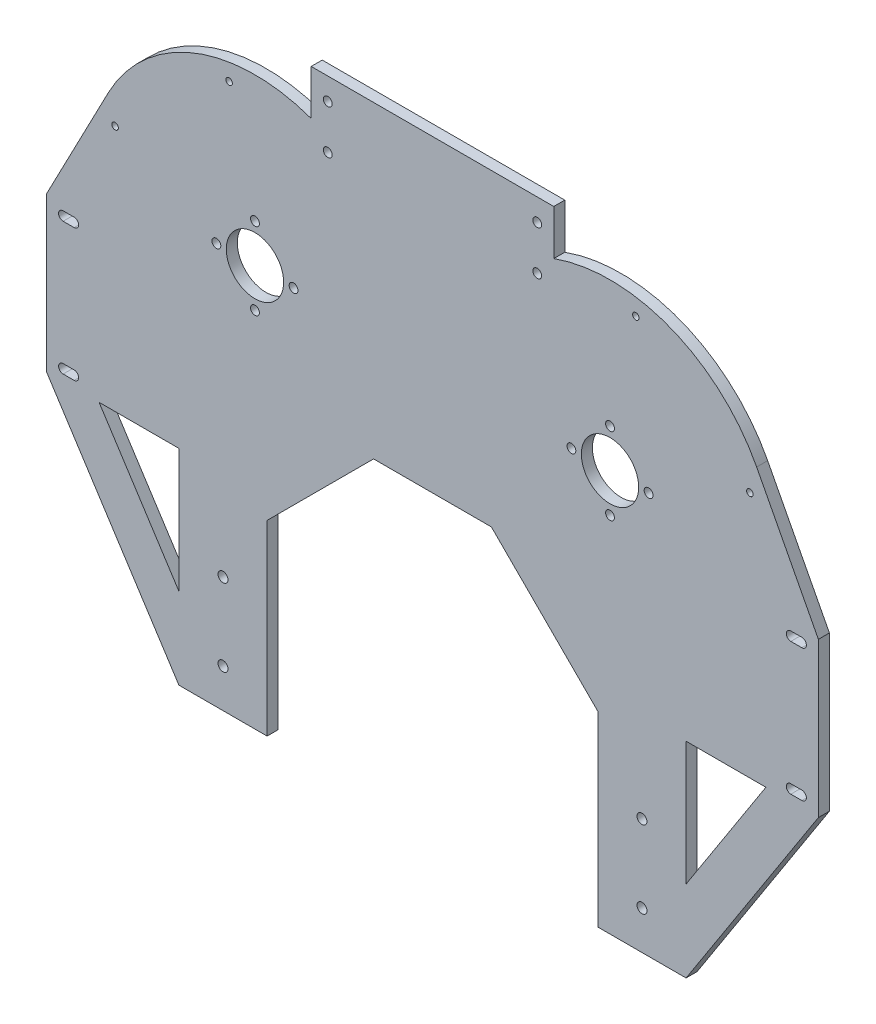
SolidWorks part; units mm, degrees
ref_plane "Front Plane" through (0, 0, 0) normal (0, 0, 1) x (1, 0, 0)
ref_plane "Top Plane" through (0, 0, 0) normal (0, 1, 0) x (1, 0, 0)
ref_plane "Right Plane" through (0, 0, 0) normal (1, 0, 0) x (0, 0, -1)
sketch "Sketch1" plane through (0, 0, 0) normal (0, 0, 1) x (1, 0, 0)
  line L1 (-100, -75) -> (100, -75)
  line L2 (-100, -75) -> (-100, 75)
  line L3 (-100, 75) -> (100, 75)
  line L4 (100, -75) -> (100, 75)
  line L5 (-100, -75) -> (100, 75) construction
  line L6 (-100, 75) -> (100, -75) construction
  line L8 (-47.5, 40) -> (47.5, 40) construction
  line L9 (0, 75) -> (0, -75) construction
  line L10 (-27, -44) -> (27, -44) construction
  line L11 (-27, -44) -> (-27, 28) construction
  line L12 (-27, 28) -> (27, 28) construction
  line L13 (27, -44) -> (27, 28) construction
  line L14 (-27, -44) -> (27, 28) construction
  line L15 (-27, 28) -> (27, -44) construction
  line L23 (-55, 70) -> (55, 70)
  line L24 (-55, 70) -> (-55, -70)
  line L25 (-55, -70) -> (55, -70)
  line L26 (55, 70) -> (55, -70)
  line L27 (-55, 70) -> (55, -70) construction
  line L28 (-55, -70) -> (55, 70) construction
  line L29 (-32.5, 70) -> (32.5, 70) construction
  line L30 (-32.5, 70) -> (-32.5, 55) construction
  line L31 (-32.5, 55) -> (32.5, 55) construction
  line L32 (32.5, 70) -> (32.5, 55) construction
  line L33 (-32.5, 70) -> (32.5, 55) construction
  line L34 (-32.5, 55) -> (32.5, 70) construction
  circle A2 centre (-47.5, 40) radius 2
  circle A3 centre (47.5, 40) radius 2
  circle A4 centre (-27, 28) radius 2 construction
  circle A5 centre (27, 28) radius 2 construction
  circle A6 centre (27, -44) radius 2 construction
  circle A7 centre (-27, -44) radius 2 construction
  circle A8 centre (-47.5, 60) radius 2
  circle A10 centre (47.5, 60) radius 2
  point P0 (0, 0)
  point P15 (0, 40)
  point P18 (0, -8)
  point P56 (0, 0)
  point P63 (0, 62.5)
  dimension "D3" = 4
  dimension "D4" = 20
  dimension "D5" = 4
  dimension "D8" = 4
  dimension "D1" = 150
  dimension "D2" = 200
  dimension "D6" = 72
  dimension "D7" = 54
  dimension "D14" = 30
  dimension "D15" = 140
  dimension "D16" = 110
  dimension "D17" = 95
  dimension "D18" = 12
  dimension "D19" = 15
  dimension "D20" = 65
extrude "Boss-Extrude1" add sketch "Sketch1" along normal blind 5 contours L23 L32 L31 L30 L24 L25 L26 A7 A6 A5 A4 A3 A2 region at (0, -0.1637, 0)
sketch "Sketch2" plane through (0, 0, 0) normal (0, 0, 1) x (1, 0, 0)
  line L0 (-55, -70) -> (-100.8579, -115.8579) construction
  line L1 (-55, 70) -> (-55, -70) construction
  line L2 (-55, -41.7157) -> (-115, -101.7157)
  line L3 (-26.7157, -70) -> (-86.7157, -130)
  line L4 (-55, -70) -> (55, -70) construction
  line L5 (-115, -101.7157) -> (-86.7157, -130)
  line L6 (-115, -101.7157) -> (-115, -203)
  line L7 (-75, -118.2843) -> (-75, -203)
  line L8 (-75, -203) -> (-115, -203)
  line L9 (0, 75) -> (0, -75) construction
  line L10 (-55, -41.7157) -> (-26.7157, -70)
  line L11 (-55, 70) -> (-55, -70) construction
  line L12 (-115, -203) -> (-75, -203) construction
  circle A0 centre (-95, -150.5) radius 2.25
  circle A1 centre (-95, -185.5) radius 2.25
  circle A2 centre (-95, -150.5) radius 2.25 construction
  circle A4 centre (-95, -185.5) radius 2.25 construction
  dimension "D1" = 135
  dimension "D2" = 40
  dimension "D3" = 40
  dimension "D4" = 75
  dimension "D5" = 0
extrude "Boss-Extrude2" add sketch "Sketch2" along normal blind 5 contours L8 L7 L3 L5 L6 | L10 L2 L5 L3 region at (-70.8579, -85.8579, 0) region at (-95.9307, -160.1869, 0)
mirror "Mirror1" about plane through (0, 0, 0) normal (1, 0, 0) of "Boss-Extrude2"
sketch "Sketch3" plane through (0, 0, 5) normal (0, 0, 1) x (1, 0, 0)
  line L0 (0, 31.3301) -> (0, 52.1198) construction
  line L1 (-80.5, -21) -> (-92.2213, 45.4745) construction
  line L2 (-80.5, -21) -> (80.5, -21) construction
  line L3 (-80.5, -21) -> (-148, -21) construction
  line L4 (-80.5, -21) -> (-143.9293, 2.0864) construction
  circle A0 centre (-80.5, -21) radius 75
  circle A1 centre (-80.5, -3.5) radius 2
  circle A2 centre (80.5, -21) radius 75
  circle A3 centre (-80.5, -21) radius 60
  circle A4 centre (80.5, -21) radius 60
  circle A5 centre (-47.5, 40) radius 2 construction
  circle A6 centre (-47.5, 40) radius 2
  circle A7 centre (47.5, 40) radius 2
  circle A8 centre (-63, -21) radius 2
  circle A9 centre (-80.5, -38.5) radius 2
  circle A10 centre (-98, -21) radius 2
  circle A11 centre (98, -21) radius 2
  circle A12 centre (80.5, -38.5) radius 2
  circle A13 centre (63, -21) radius 2
  circle A14 centre (80.5, -3.5) radius 2
  circle A15 centre (-80.5, -21) radius 13
  circle A16 centre (80.5, -21) radius 13
  circle A17 centre (-92.2213, 45.4745) radius 1.4732
  circle A18 centre (-143.9293, 2.0864) radius 1.4732
  circle A19 centre (-80.5, -21) radius 67.5 construction
  circle A20 centre (92.2213, 45.4745) radius 1.4732
  circle A21 centre (143.9293, 2.0864) radius 1.4732
  point P28 (-80.5, -21)
  line M3 (115, -101.7157) -> (55, -41.7157)
  line M4 (55, -41.7157) -> (55, 70)
  line M6 (-55, 70) -> (-55, -41.7157)
  line M7 (-55, -41.7157) -> (-115, -101.7157)
  line M11 (-75, -118.2843) -> (-26.7157, -70)
  line M12 (-26.7157, -70) -> (26.7157, -70)
  line M13 (26.7157, -70) -> (75, -118.2843)
  circle M17 centre (-47.5, 40) radius 2
  circle M18 centre (47.5, 40) radius 2
  dimension "D1" = 161
  dimension "D2" = 150
  dimension "D3" = 61
  dimension "D4" = 120
  dimension "D5" = 4
  dimension "D7" = 35
  dimension "D8" = 26
  dimension "D9" = 7.5
  dimension "D10" = 2.9464
  dimension "D6" = 4
  dimension "D11" = 80
  dimension "D12" = 20
extrude "Boss-Extrude3" add sketch "Sketch3" against normal up to surface (5 mm away) contours A3 M6 M7 | A3 A0 M6 M7 | A3 A0 M7 M11 M12 M6 M17 | A3 M7 M6 | A4 M3 M4 | A4 M4 M3 | A4 A2 M4 M3 | A4 A2 M3 M4 M12 M13 M18 region at (-11.8554, -46.5242, 5) region at (9.6495, -2.4591, 5) region at (-56.7712, 41.4218, 5) region at (-96.2806, -16.4848, 5) region at (-46.5969, -30.7004, 5) region at (122.5668, 38.9404, 5) region at (46.5969, -30.7004, 5) region at (96.2806, -16.4848, 5) up to face at (0, -95.388, 0)
sketch "Sketch4" plane through (0, 0, 5) normal (0, 0, 1) x (1, 0, 0)
  line L0 (-175, -75) -> (-100, -75) construction
  line L1 (-100, -40) -> (-153.0534, -40)
  line L2 (-100, -40) -> (-100, -110)
  line L3 (-100, -110) -> (-115, -110) construction
  line L4 (-175, -40) -> (-175, -110)
  line L5 (-100, -40) -> (-175, -110) construction
  line L6 (-100, -110) -> (-175, -40) construction
  line L7 (-175, -110) -> (-115, -203)
  line L8 (-151.1989, -110) -> (-115, -166.1083)
  line L9 (-115, -101.7157) -> (-115, -203) construction
  line L10 (-115, -166.1083) -> (-115, -203)
  line L11 (-175, -40) -> (-146.9976, 13.6853)
  line L12 (-153.0534, -40) -> (-175, -40)
  line L13 (-100, -110) -> (-115, -110) construction
  line L14 (-100, -110) -> (-100, -101.7157)
  line L15 (-100, -101.7157) -> (-115, -101.7157)
  line L16 (-115, -110) -> (-115, -101.7157)
  line L17 (-100, -110) -> (-115, -101.7157) construction
  line L18 (-100, -101.7157) -> (-115, -110) construction
  line L19 (-151.1989, -110) -> (-175, -110) construction
  line L20 (-115, -110) -> (-151.1989, -110)
  line L21 (-165, -75) -> (-165, -40) construction
  line L22 (-162.5, -45) -> (-167.5, -45) construction
  line L23 (-162.5, -47.05) -> (-167.5, -47.05)
  line L24 (-162.5, -42.95) -> (-167.5, -42.95)
  line L25 (-162.5, -105) -> (-167.5, -105) construction
  line L26 (-162.5, -102.95) -> (-167.5, -102.95)
  line L27 (-162.5, -107.05) -> (-167.5, -107.05)
  arc A0 (-55, 49.5319) -> (-105.1261, -91.8418) centre (-80.5, -21) ccw construction
  arc A1 (-146.9976, 13.6853) -> (-153.0534, -40) centre (-80.5, -21) ccw
  circle A2 centre (-165, -45) radius 2.05 construction
  arc A3 (-162.5, -47.05) -> (-162.5, -42.95) centre (-162.5, -45) ccw
  arc A4 (-167.5, -42.95) -> (-167.5, -47.05) centre (-167.5, -45) ccw
  arc A5 (-162.5, -102.95) -> (-162.5, -107.05) centre (-162.5, -105) cw
  arc A6 (-167.5, -107.05) -> (-167.5, -102.95) centre (-167.5, -105) cw
  point P4 (-137.5, -75)
  point P23 (-107.5, -105.8579)
  point P32 (-165, -45)
  point P37 (0, 0)
  point P40 (-165, -105)
  point P45 (-159.6786, -56.7407)
  arc M12 (-55, 49.5319) -> (-105.1261, -91.8418) centre (-80.5, -21) ccw
  line M13 (-105.1261, -91.8418) -> (-115, -101.7157)
  line M14 (-115, -101.7157) -> (-115, -203)
  circle M41 centre (-143.9293, 2.0864) radius 1.4732
  dimension "D7" = 4.1
  dimension "D8" = 2.05
  dimension "D1" = 40
  dimension "D2" = 100
  dimension "D3" = 70
  dimension "D4" = 75
  dimension "D5" = 20
  dimension "D6" = 10
  dimension "D9" = 5
  dimension "D10" = 5
extrude "Boss-Extrude5" add sketch "Sketch4" against normal up to surface (5 mm away) contours L20 L16 L12 L4 L7 L8 A4 L24 A3 L23 L27 A6 L26 A5 M13 M12 M14 | L15 L14 L2 L1 M12 M13 M41 | L12 L11 M12 region at (-120.1023, -62.6792, 5) region at (-145.9871, -106.3764, 5) region at (-161.1873, -26.2241, 5) up to face at (0, -80.3864, 0)
mirror "Mirror2" about plane through (0, 0, 0) normal (1, 0, 0) of "Boss-Extrude5"
